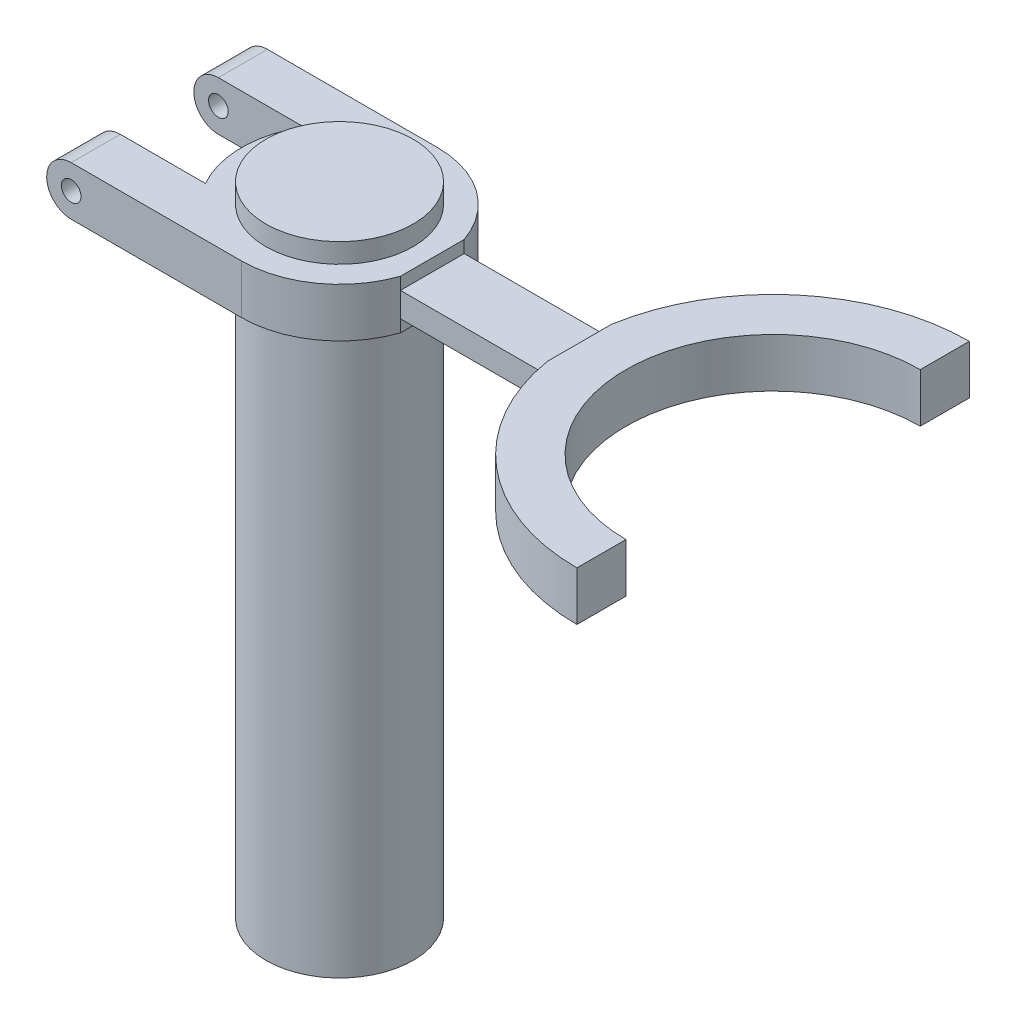
SolidWorks part; units mm, degrees
ref_plane "Front Plane" through (0, 0, 0) normal (0, 0, 1) x (1, 0, 0)
ref_plane "Top Plane" through (0, 0, 0) normal (0, 1, 0) x (1, 0, 0)
ref_plane "Right Plane" through (0, 0, 0) normal (1, 0, 0) x (0, 0, -1)
sketch "Sketch2" plane through (0, 0, 0) normal (0, 1, 0) x (1, 0, 0)
  line L0 (0, 0) -> (88.3826, 0) construction
  line L1 (88.3826, 40) -> (88.3826, -40)
  line L2 (0, 0) -> (-136.594, 0) construction
  line L3 (-39.7, -10) -> (-39.7, -20)
  line L4 (0, 20) -> (-39.7, 20)
  line L5 (0, 20) -> (0, -20)
  line L6 (0, -20) -> (-39.7, -20)
  line L7 (-39.7, 20) -> (-39.7, 10)
  line L8 (-17.3205, 10) -> (-39.7, 10)
  line L12 (-17.3205, -10) -> (-39.7, -10)
  line L13 (18.9143, 6.5) -> (48.9143, 6.5)
  line L15 (18.9143, -6.5) -> (48.9143, -6.5)
  circle A0 centre (0, 0) radius 15
  arc A1 (-17.3205, 10) -> (-17.3205, -10) centre (0, 0) ccw
  arc A2 (88.3826, 40) -> (88.3826, -40) centre (88.3826, 0) ccw
  arc A3 (88.3826, 30) -> (88.3826, -30) centre (88.3826, 0) ccw
  arc A4 (0, -20) -> (0, 20) centre (0, 0) ccw
  point P18 (-17.3205, -10)
  point P22 (-17.3205, -10)
  dimension "D1" = 30
  dimension "D2" = 40
  dimension "D3" = 80
  dimension "D4" = 60
  dimension "D5" = 40
  dimension "D6" = 20
  dimension "D7" = 39.7
  dimension "D8" = 30
  dimension "D9" = 13
  dimension "D10" = 22.3795
extrude "Boss-Extrude3" add sketch "Sketch2" along normal blind 10 contours L8 A1 L12 L3 L6 L5 A0 L4 L7 | L5 A4 A0 | A3 L1 A2 | A4 L15 A2 L13 region at (87.4882, 0, -35) region at (34.0994, 0, 0) region at (19.5528, 0, 0) region at (-0.5636, 0, -17.5)
sketch "Sketch4" plane through (0, 0, 20) normal (0, 0, 1) x (1, 0, 0)
  line L0 (-39.7, 5) -> (0, 5) construction
  line L1 (-39.7, 10) -> (-39.7, 0) construction
  line L2 (0, 10) -> (0, 0) construction
  line L3 (0, 0) -> (-39.7, 0) construction
  line L4 (0, 10) -> (-39.7, 10) construction
  line L5 (-39.7, 10) -> (-39.7, 0)
  line L6 (0, 0) -> (-39.7, 0)
  line L7 (0, 10) -> (-39.7, 10)
  circle A0 centre (-34.7, 5) radius 5
  circle A1 centre (-34.7, 5) radius 2
  line M1 (-39.7, 0) -> (0, 0)
  line M4 (-39.7, 10) -> (-39.7, 0)
  dimension "D1" = 4
extrude "Cut-Extrude2" cut sketch "Sketch4" against normal through all both contours A0 L7 M4 | A0 L5 M1 | L0 A1 | A1 L0 region at (-34.7, 4.1512, 20) region at (-34.7, 5.8488, 20) region at (-38.5832, 8.8832, 20) region at (-38.5832, 1.1168, 20)
extrude "Boss-Extrude5" add sketch "Sketch2<6>" along normal blind 14 contours L5 A0 | L5 A0 region at (6.3662, 0, 0) region at (-6.3662, 0, 0)
sketch "Sketch2<6>" plane through (0, 0, 0) normal (0, 1, 0) x (1, 0, 0) same geometry as "Sketch2"
sketch "Sketch5" plane through (0, 0, 0) normal (0, -1, 0) x (1, 0, 0)
  circle A0 centre (0, 0) radius 15
  dimension "D1" = 30
extrude "Boss-Extrude6" add sketch "Sketch5" along normal blind 116
sketch "Sketch6" plane through (0, 0, 6.5) normal (0, 0, 1) x (1, 0, 0)
  line L0 (18.9143, 10) -> (18.9143, 0)
  line L1 (48.9143, 10) -> (48.9143, 0)
  line L2 (18.9143, 5) -> (48.9143, 5) construction
  line L3 (18.9143, 0) -> (48.9143, 0) construction
  line L4 (18.9143, 7.5) -> (48.9143, 7.5)
  line L5 (18.9143, 7.5) -> (18.9143, 2.5)
  line L6 (18.9143, 2.5) -> (48.9143, 2.5)
  line L7 (48.9143, 7.5) -> (48.9143, 2.5)
  line L8 (18.9143, 10) -> (48.9143, 10) construction
  line L9 (18.9143, 0) -> (48.9143, 0)
  line L10 (18.9143, 10) -> (48.9143, 10)
  line M2 (18.9143, 0) -> (48.9143, 0)
  line M3 (48.9143, 0) -> (48.9143, 10)
  line M4 (48.9143, 10) -> (18.9143, 10)
  line M5 (18.9143, 10) -> (18.9143, 0)
  dimension "D1" = 5
extrude "Cut-Extrude3" cut sketch "Sketch6" against normal through all both and the other way through all contours L4 L1 M5 M4 | L6 M5 M2 M3 region at (33.9143, 8.75, 6.5) region at (33.9143, 1.25, 6.5)
